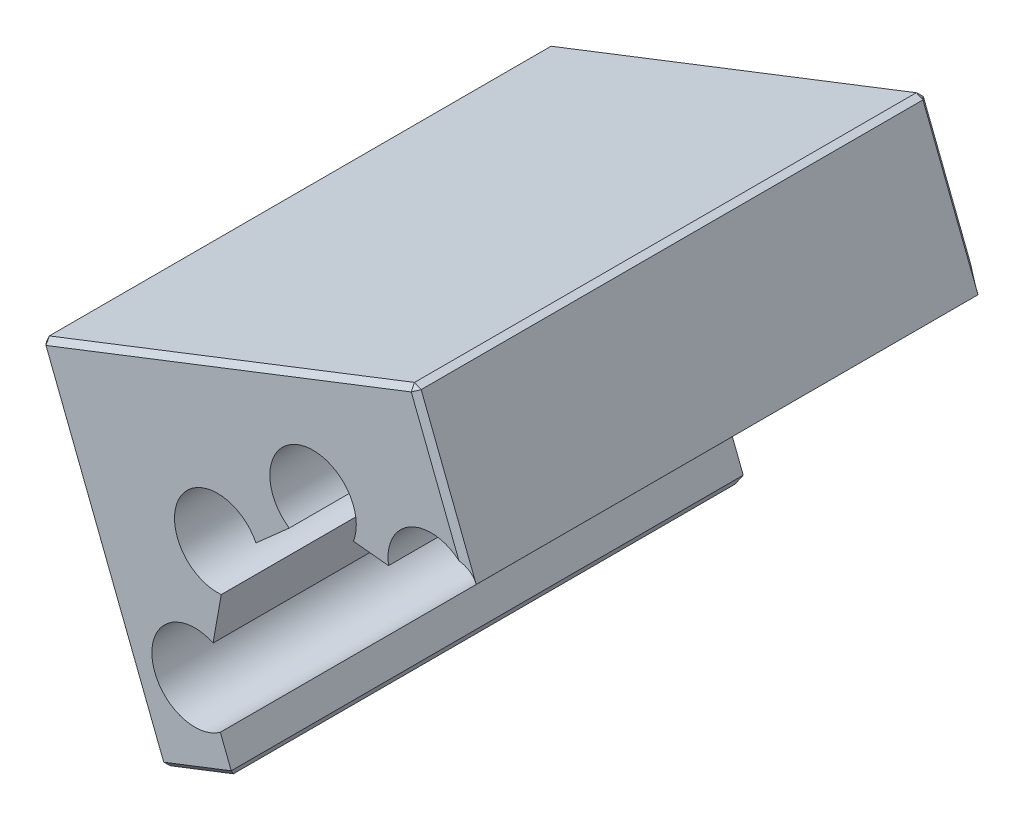
SolidWorks part; units mm, degrees
ref_plane "前基準面" through (0, 0, 0) normal (0, 0, 1) x (1, 0, 0)
ref_plane "上基準面" through (0, 0, 0) normal (0, 1, 0) x (1, 0, 0)
ref_plane "右基準面" through (0, 0, 0) normal (1, 0, 0) x (0, 0, -1)
sketch "草圖1" plane through (0, 0, 12886.3827) normal (0, 0, 1) x (1, 0, 0)
  line L0 (-121.0055, -94.6668) -> (-109.956, -32.2463) construction
  line L1 (-109.956, -32.2463) -> (-63.2989, 9.2018) construction
  line L2 (-63.2989, 9.2018) -> (-5.7089, 3.2255) construction
  line L3 (-121.0055, -94.6668) -> (-112.1178, -75.6402) construction
  line L4 (-112.1178, -75.6402) -> (-108.1397, -53.1676)
  line L5 (-108.1397, -53.1676) -> (-109.956, -32.2463) construction
  line L6 (-109.956, -32.2463) -> (-91.1815, -22.8379) construction
  line L7 (-91.1815, -22.8379) -> (-74.9152, -8.4262)
  line L8 (-74.9152, -8.4262) -> (-63.2989, 9.2018) construction
  line L9 (-63.2989, 9.2018) -> (-43.5799, 1.6622) construction
  line L10 (-43.5799, 1.6622) -> (-26.446, -0.0869)
  line L11 (-26.446, -0.0869) -> (-5.7089, 3.2255) construction
  line L12 (-108.5754, -111.5928) -> (-102.3514, -127.5624)
  line L14 (13.8576, 10.8513) -> (-13.9295, 82.1483)
  line L15 (-102.3514, -127.5624) -> (-137.6384, -141.3151)
  line L16 (-137.6384, -141.3151) -> (-196.9331, 10.825)
  line L17 (-196.9331, 10.825) -> (-13.9295, 82.1483)
  arc A1 (-112.1178, -75.6402) -> (-108.5754, -111.5928) centre (-121.0055, -94.6668) ccw
  arc A2 (-91.1815, -22.8379) -> (-108.1397, -53.1676) centre (-109.956, -32.2463) ccw
  arc A3 (-43.5799, 1.6622) -> (-74.9152, -8.4262) centre (-63.2989, 9.2018) ccw
  arc A4 (13.8576, 10.8513) -> (-26.446, -0.0869) centre (-5.7089, 3.2255) ccw
  dimension "D1" = 15
  dimension "D2" = 15
  dimension "D3" = 15
  dimension "D4" = 15
  dimension "D5" = 15
  dimension "D6" = 15
extrude "填料-伸長2" add sketch "草圖1" against normal blind 250
chamfer "導角1" distance 2.5 angle 45 12 edges at (-105.4313, 46.4867, 12636.3827) (-0.036, 46.4998, 12636.3827) (-13.9295, 82.1483, 12761.3827) (-167.2857, -65.245, 12636.3827) (-196.9331, 10.825, 12761.3827) (-102.3514, -127.5624, 12761.3827) (-119.9949, -134.4387, 12636.3827) (-137.6384, -141.3151, 12761.3827) (-119.9949, -134.4387, 12886.3827) (-167.2857, -65.245, 12886.3827) (-105.4313, 46.4867, 12886.3827) (-0.036, 46.4998, 12886.3827)
equation "\"ㄉ200\"=10"
